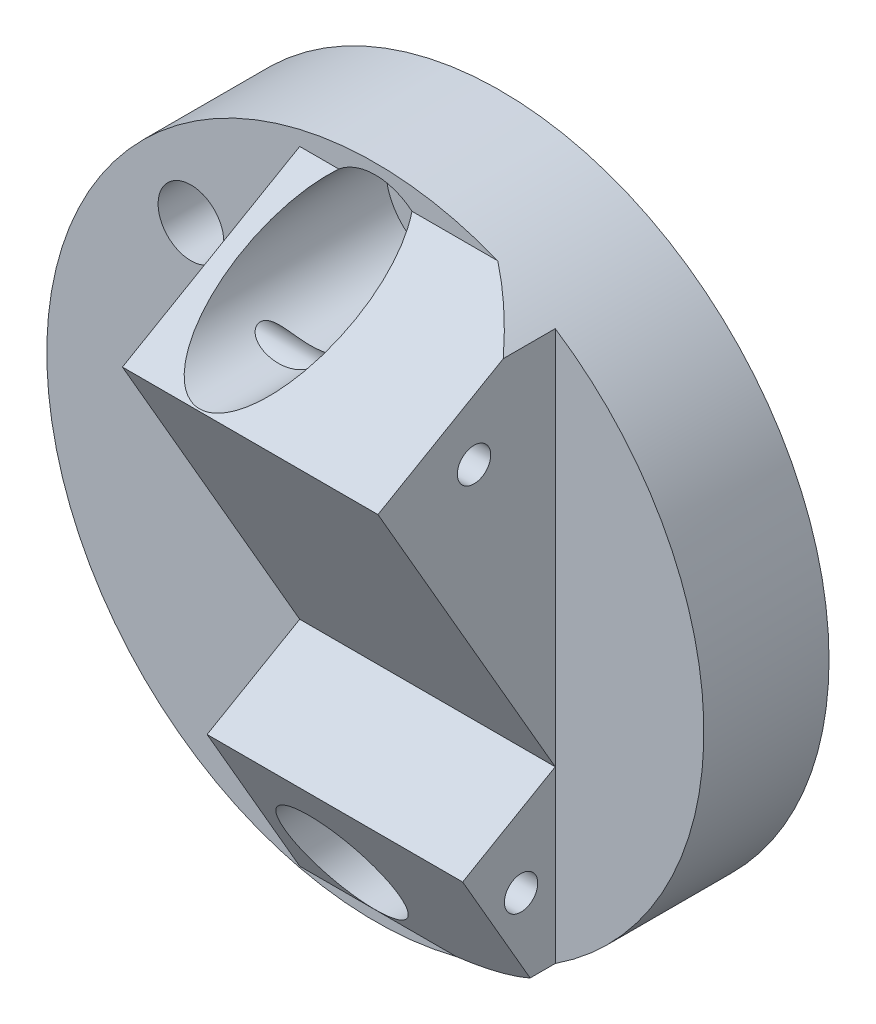
SolidWorks part; units mm, degrees
ref_plane "Front Plane" through (0, 0, 0) normal (0, 0, 1) x (1, 0, 0)
ref_plane "Top Plane" through (0, 0, 0) normal (0, 1, 0) x (1, 0, 0)
ref_plane "Right Plane" through (0, 0, 0) normal (1, 0, 0) x (0, 0, -1)
sketch "Sketch1" plane through (0, 0, 0) normal (0, 0, 1) x (1, 0, 0)
  line L0 (0, 0) -> (-17.6777, 17.6777) construction
  line L1 (0, 0) -> (0, 25) construction
  circle A0 centre (0, 0) radius 31.5
  circle A1 centre (0, 0) radius 25 construction
  dimension "D1" = 63
  dimension "D2" = 50
  dimension "D3" = 45
sketch "Sketch2" plane through (0, 0, 0) normal (0, 0, 1) x (1, 0, 0)
  circle A0 centre (0, 0) radius 31.5 construction
  circle A1 centre (0, 0) radius 31.5
extrude "Boss-Extrude1" add sketch "Sketch2" along normal blind 12
hole_wizard "CBORE for M6 SHCS1" positions "Sketch3" profile "Sketch4" counterbore size "M6" standard "ANSI Metric" end condition through all
sketch "Sketch3" plane through (0, 0, 12) normal (0, 0, 1) x (1, 0, 0)
  circle A0 centre (0, 0) radius 25 construction
  point P0 (0, 25)
  point P3 (0, -25)
sketch "Sketch4" plane through (0, 25, 12) normal (1, 0, 0) x (0, -1, 0)
  line L0 (0, 0) -> (0, 12)
  line L1 (0, 12) -> (3.2, 12)
  line L3 (3.2, 12) -> (3.2, 6.5)
  line L4 (3.2, 6.5) -> (5.5, 6.5)
  line L5 (5.5, 6.5) -> (5.5, 0)
  line L7 (5.5, 0) -> (0, 0)
  line L11 (0, -6.35) -> (0, 107.95) construction
  dimension "Thru Hole Dia." = 6.4
  dimension "Thru Hole Depth" = 12
  dimension "C'Bore Dia." = 11
  dimension "C'Bore Depth" = 6.5
sketch "Sketch5" plane through (0, 0, 0) normal (0, 0, -1) x (-1, 0, 0)
  circle A0 centre (17.6777, 17.6777) radius 3.15
  dimension "D1" = 6.3
extrude "Cut-Extrude1" cut sketch "Sketch5" against normal up to surface (12 mm away) up to face at (5.5, 25, 12)
ref_plane "Plane1" through (17.25, 0, 0) normal (1, 0, 0) x (0, 0, -1)
sketch "Sketch6" plane through (17.25, 0, 0) normal (1, 0, 0) x (0, 0, -1)
  line L0 (-12, 29.2319) -> (-28.9984, 19.4179)
  line L1 (-12, 31.5) -> (-12, -31.5) construction
  line L2 (-28.9984, 19.4179) -> (-12, -10.0242)
  line L3 (-12, -10.0242) -> (-12, 29.2319)
  dimension "D1" = 30
  dimension "D2" = 10.0242
  dimension "D3" = 33.9968
extrude "Boss-Extrude2" add sketch "Sketch6" against normal blind 24.5
sketch "Sketch7" plane through (0, 0, 12) normal (0, 0, 1) x (1, 0, 0)
  circle A0 centre (0, 25) radius 5.5 construction
  circle A1 centre (0, 25) radius 5.5
extrude "Cut-Extrude2" cut sketch "Sketch7" along normal blind 65
sketch "Sketch8" plane through (17.25, 0, 0) normal (1, 0, 0) x (0, 0, -1)
  line L0 (-12, -10.0242) -> (-20.8781, -15.15)
  line L1 (-20.8781, -15.15) -> (-12, -30.5273)
  line L2 (-12, 31.5) -> (-12, -31.5) construction
  line L3 (-12, -30.5273) -> (-12, -10.0242)
  line L4 (-28.9984, 19.4179) -> (-12, -10.0242) construction
  dimension "D1" = 10.2515
extrude "Boss-Extrude3" add sketch "Sketch8" against normal up to surface (24.5 mm away) up to face at (-7.25, 12.8752, 17.6661)
sketch "Sketch9" plane through (0, 0, 12) normal (0, 0, 1) x (1, 0, 0)
  circle A0 centre (0, -25) radius 5.5 construction
  circle A1 centre (0, -25) radius 5.5
extrude "Cut-Extrude3" cut sketch "Sketch9" along normal blind 82
sketch "Sketch11" plane through (0, 0, 0) normal (0, 0, -1) x (-1, 0, 0)
  circle A0 centre (0, 0) radius 31.5 construction
  circle A1 centre (0, 0) radius 31.5
  circle A2 centre (0, 0) radius 51.4472
extrude "Cut-Extrude4" cut sketch "Sketch11" against normal blind 82
sketch "Sketch12" plane through (-7.25, 0, 0) normal (-1, 0, 0) x (0, 0, 1)
  circle A0 centre (19.7883, 18.9639) radius 1.6 construction
  circle A1 centre (19.7883, 18.9639) radius 1.6
  circle A2 centre (15.2787, -18.847) radius 1.6 construction
  circle A3 centre (15.2787, -18.847) radius 1.6
extrude "Cut-Extrude5" cut sketch "Sketch12" against normal blind 52
